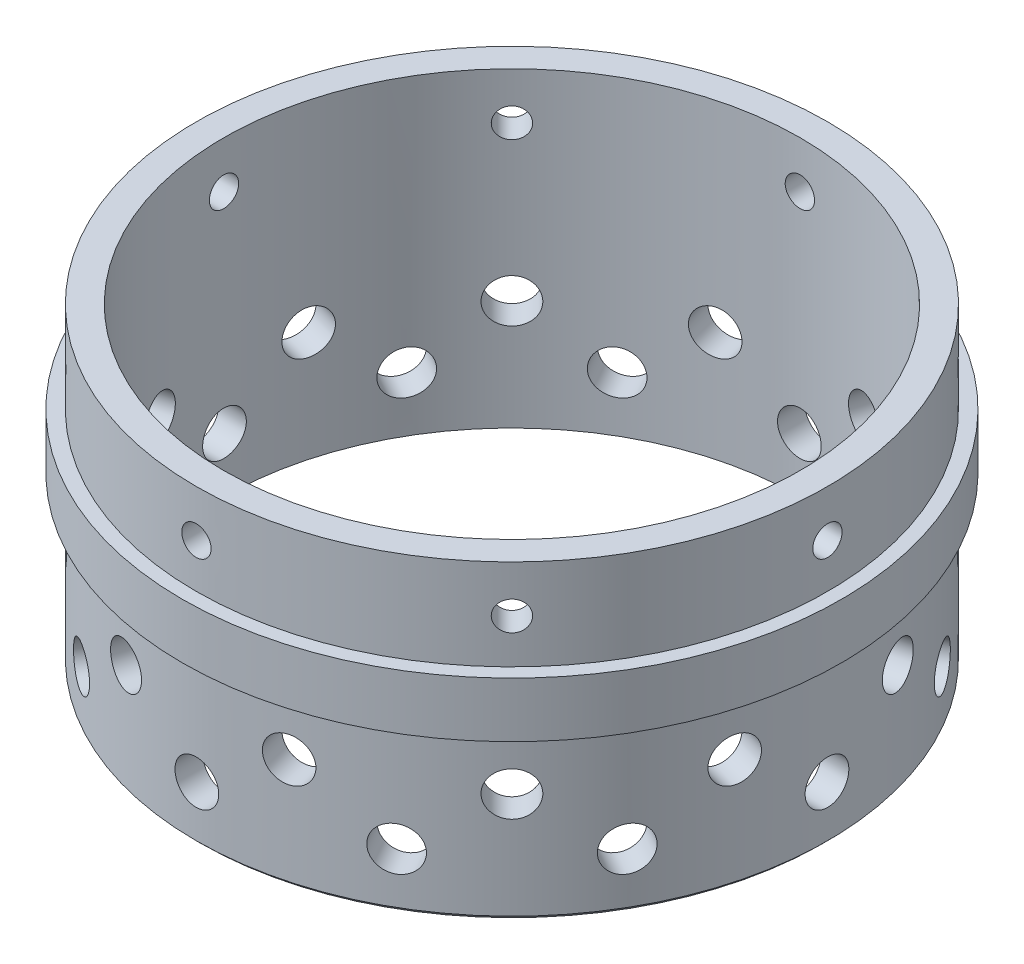
SolidWorks part; units mm, degrees
material "6061-T6 (SS)"
ref_plane "Front Plane" through (0, 0, 0) normal (0, 0, 1) x (1, 0, 0)
ref_plane "Top Plane" through (0, 0, 0) normal (0, 1, 0) x (1, 0, 0)
ref_plane "Right Plane" through (0, 0, 0) normal (1, 0, 0) x (0, 0, -1)
sketch "Sketch1" plane through (0, 0, 0) normal (0, 1, 0) x (1, 0, 0)
  circle A0 centre (0, 0) radius 66.4845
  circle A1 centre (0, 0) radius 76.0095
  circle A2 centre (0, 0) radius 72.8345
  dimension "D1" = 152.019
  dimension "D2" = 3.175
  dimension "D3" = 6.35
extrude "Boss-Extrude1" add sketch "Sketch1" along normal blind 12.7 contours A2 A0 | A1 A2 region at (-73.8596, 0, 0) region at (-70.7744, 0, 0)
extrude "Boss-Extrude2" add sketch "Sketch1<3>" against normal blind 38.1 contours A2 A0 region at (-70.7744, 0, 0)
sketch "Sketch1<3>" plane through (0, 0, 0) normal (0, 1, 0) x (1, 0, 0) same geometry as "Sketch1"
extrude "Boss-Extrude3" add sketch "Sketch1<4>" along normal blind 33.655 contours A2 A0 region at (-70.7744, 0, 0)
sketch "Sketch1<4>" plane through (0, 0, 0) normal (0, 1, 0) x (1, 0, 0) same geometry as "Sketch1"
chamfer "Chamfer1" distance 1 angle 45 1 edges at (0, -38.1, 72.8345)
sketch "Sketch2" plane through (0, 0, 0) normal (0, 0, 1) x (1, 0, 0)
  line L0 (0, 0) -> (0, 22.86) construction
  line L1 (0, 0) -> (0, -25.4) construction
  line L2 (-71.8345, -38.1) -> (71.8345, -38.1) construction
  line L3 (72.8345, 33.655) -> (-72.8345, 33.655) construction
  circle A0 centre (0, 22.86) radius 3.3782
  circle A1 centre (0, -25.4) radius 5.0419
  dimension "D1" = 6.7564
  dimension "D2" = 10.0838
  dimension "D3" = 25.4
  dimension "D5" = 12.7
  dimension "D4" = 10.795
extrude "Cut-Extrude1" cut sketch "Sketch2" against normal through all contours A1 region at (0, -25.4, 0)
ref_plane "Plane1" through (-19.6727, 0, 73.4195) normal (-0.2588, 0, 0.9659) x (0, -1, 0)
sketch "Sketch3" plane through (-19.6727, 0, 73.4195) normal (-0.2588, 0, 0.9659) x (0, -1, 0)
  line L0 (12.7, 0) -> (0, 0) construction
  line L1 (38.1, -71.8345) -> (38.1, 71.8345) construction
  circle A0 centre (12.7, 0) radius 5.0419
  dimension "D3" = 25.4
  dimension "D1" = 10.0838
  dimension "D2" = 12.7
extrude "Cut-Extrude2" cut sketch "Sketch3" against normal blind 38.1
pattern_circular "CirPattern2" count 12 over 360 of "Cut-Extrude2", "Cut-Extrude1" reverse direction yes
extrude "Cut-Extrude3" cut sketch "Sketch2<3>" against normal through all contours A0
sketch "Sketch2<3>" plane through (0, 0, 0) normal (0, 0, 1) x (1, 0, 0) same geometry as "Sketch2"
pattern_circular "CirPattern3" count 8 over 360 about axis through (0, 12.7, 0) along (0, -1, 0) of "Cut-Extrude3"
equation "\"holeDia\"= 0.397in"
equation "\"D2@Sketch2\"=\"holeDia\""
equation "\"numHoles\"=12"
equation "\"D1@Plane1\"=180/\"numHoles\""
equation "\"D1@Sketch3\"=\"holeDia\""
equation "\"D1@CirPattern2\"=\"numHoles\""
